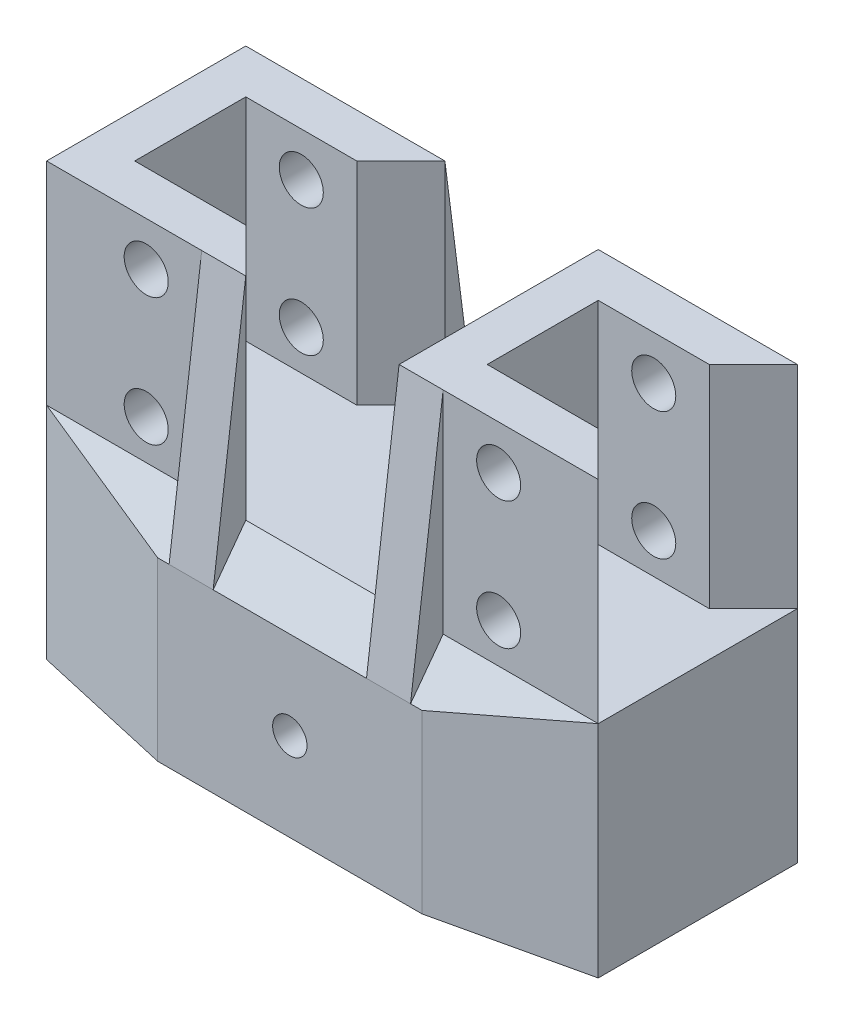
SolidWorks part; units mm, degrees
ref_plane "Front Plane" through (0, 0, 0) normal (0, 0, 1) x (1, 0, 0)
ref_plane "Top Plane" through (0, 0, 0) normal (0, 1, 0) x (1, 0, 0)
ref_plane "Right Plane" through (0, 0, 0) normal (1, 0, 0) x (0, 0, -1)
sketch "Sketch1" plane through (0, 0, 0) normal (0, 1, 0) x (1, 0, 0)
  line L0 (-20, 0) -> (20, 0)
  line L1 (-31.3, 11.3) -> (-8.7, 11.3)
  line L2 (-26.3, -6.3) -> (-13.7, -6.3)
  line L3 (-26.3, -6.3) -> (-26.3, 6.3)
  line L4 (-26.3, 6.3) -> (-13.7, 6.3)
  line L5 (-13.7, -6.3) -> (-13.7, 6.3)
  line L6 (-26.3, -6.3) -> (-13.7, 6.3) construction
  line L7 (-26.3, 6.3) -> (-13.7, -6.3) construction
  line L8 (13.7, -6.3) -> (26.3, -6.3)
  line L9 (13.7, -6.3) -> (13.7, 6.3)
  line L10 (13.7, 6.3) -> (26.3, 6.3)
  line L11 (26.3, -6.3) -> (26.3, 6.3)
  line L12 (13.7, -6.3) -> (26.3, 6.3) construction
  line L13 (13.7, 6.3) -> (26.3, -6.3) construction
  line L14 (-8.7, -11.3) -> (-8.7, 11.3)
  line L15 (-31.3, -11.3) -> (-8.7, -11.3)
  line L16 (-31.3, -11.3) -> (-31.3, 11.3)
  line L17 (8.7, 11.3) -> (31.3, 11.3)
  line L18 (31.3, -11.3) -> (31.3, 11.3)
  line L19 (8.7, -11.3) -> (31.3, -11.3)
  line L20 (8.7, -11.3) -> (8.7, 11.3)
  line L21 (-13.7, 6.3) -> (-8.7, 11.3)
  line L22 (-13.7, -6.3) -> (-8.7, -11.3)
  line L23 (26.3, -6.3) -> (31.3, -11.3)
  line L24 (26.3, 6.3) -> (31.3, 11.3)
  point P4 (0, 0)
  dimension "D1" = 40
  dimension "D2" = 12.6
  dimension "D3" = 12.6
  dimension "D4" = 12.6
  dimension "D5" = 12.6
  dimension "D6" = 5
extrude "Boss-Extrude1" add sketch "Sketch1" along normal blind 24 contours L22 L2 L3 L4 L21 L1 L16 L15 | L10 L24 L17 L20 L0 L9 | L23 L8 L9 L0 L20 L19 region at (16.9878, 0, -7.5306) region at (16.9878, 0, 7.5306) region at (-11.426, 0, 9.026)
sketch "Sketch2" plane through (0, 0, 11.3) normal (0, 0, 1) x (1, 0, 0)
  line L0 (-20, 23.5) -> (-20, 19)
  line L1 (-20, 19) -> (-20, 4.5)
  line L2 (-20, 4.5) -> (-20, 0)
  line L3 (-31.3, 0) -> (-8.7, 0) construction
  line L4 (0, -12.43) -> (0, 12.43) construction
  line L5 (20, 4.5) -> (20, 0)
  line L6 (20, 19) -> (20, 4.5)
  circle A0 centre (-20, 19) radius 2.5
  circle A1 centre (-20, 4.5) radius 2.5
  circle A2 centre (20, 4.5) radius 2.5
  circle A3 centre (20, 19) radius 2.5
  point P9 (-20, 0)
  dimension "D1" = 5
  dimension "D2" = 5
  dimension "D3" = 14.5
  dimension "D4" = 4.5
  dimension "D5" = 0
  dimension "D6" = 4.5
extrude "Cut-Extrude1" cut sketch "Sketch2" against normal through all contours L1 A0 L0 | L0 A0 L1 | L2 A1 L1 | L1 A1 L2 | A2 L5 L6 | A2 L6 L5 | A3 region at (-18.939, 19, 11.3) region at (-18.939, 4.5, 11.3) region at (-21.061, 4.5, 11.3) region at (-21.061, 19, 11.3) region at (21.061, 4.5, 11.3) region at (18.939, 4.5, 11.3) region at (18.2822, 20.7178, 11.3)
sketch "Sketch3" plane through (0, 0, 0) normal (0, -1, 0) x (1, 0, 0)
  line L1 (-31.3, -11.3) -> (31.3, -11.3)
  line L2 (-31.3, -11.3) -> (-31.3, 11.3)
  line L3 (-31.3, 11.3) -> (31.3, 11.3)
  line L4 (31.3, -11.3) -> (31.3, 11.3)
  line L5 (-31.3, -11.3) -> (31.3, 11.3) construction
  line L6 (-31.3, 11.3) -> (31.3, -11.3) construction
  point P0 (0, 0)
extrude "Boss-Extrude2" add sketch "Sketch3" along normal blind 5
sketch "Sketch4" plane through (0, -5, 0) normal (0, -1, 0) x (1, 0, 0)
  line L0 (-15, -15) -> (-15, 15)
  line L1 (-10, -10) -> (10, -10)
  line L2 (-10, -10) -> (-10, 10)
  line L3 (-10, 10) -> (10, 10)
  line L4 (10, -10) -> (10, 10)
  line L5 (-10, -10) -> (10, 10) construction
  line L6 (-10, 10) -> (10, -10) construction
  line L7 (-15, 15) -> (15, 15)
  line L8 (15, -15) -> (15, 15)
  line L9 (-15, -15) -> (15, -15)
  point P0 (0, 0)
  dimension "D1" = 20
  dimension "D2" = 20
  dimension "D3" = 5
extrude "Boss-Extrude3" add sketch "Sketch4" along normal blind 20
sketch "Sketch6" plane through (0, -25, 0) normal (0, -1, 0) x (1, 0, 0)
  line L0 (15, 15) -> (31.3, 11.3)
  line L1 (31.3, 11.3) -> (31.3, -11.3)
  line L2 (31.3, -11.3) -> (15, -15)
  line L3 (15, -15) -> (-15, -15)
  line L4 (-15, -15) -> (-31.3, -11.3)
  line L5 (-31.3, -11.3) -> (-31.3, 11.3)
  line L6 (-31.3, 11.3) -> (-15, 15)
  line L7 (-15, 15) -> (15, 15)
  line L9 (-10, -10) -> (10, -10)
  line L10 (-10, -10) -> (-10, 10)
  line L11 (-10, 10) -> (10, 10)
  line L12 (10, -10) -> (10, 10)
  line L13 (-10, -10) -> (10, 10) construction
  line L14 (-10, 10) -> (10, -10) construction
  point P4 (0, 0)
extrude "Boss-Extrude4" add sketch "Sketch6" against normal blind 20
sketch "Sketch8" plane through (0, -5, 0) normal (0, -1, 0) x (1, 0, 0)
  line L0 (4, -2.5) -> (4, 2.5)
  line L1 (8, -2.3555) -> (8, 2.3555)
  line L2 (8, -5) -> (8, 5)
  line L3 (4, 2.5) -> (8, 5)
  line L4 (4, -2.5) -> (8, -5)
  line L5 (8, -2.3555) -> (10, -2.3555)
  line L6 (8, 2.3555) -> (10, 2.3555)
  line L7 (10, 2.3555) -> (10, -2.3555)
  line L8 (10, -10) -> (10, 10) construction
  line L9 (-10, -10) -> (10, -10) construction
  line L10 (-2.3555, -8) -> (2.3555, -8)
  line L11 (2.3555, -8) -> (2.3555, -10)
  line L12 (2.3555, -10) -> (-2.3555, -10)
  line L13 (-2.3555, -8) -> (-2.3555, -10)
  line L14 (-2.5, -4) -> (2.5, -4)
  line L15 (2.5, -4) -> (5, -8)
  line L16 (-5, -8) -> (5, -8)
  line L17 (-2.5, -4) -> (-5, -8)
  line L18 (-8, 2.3555) -> (-8, -2.3555)
  line L19 (-8, -2.3555) -> (-10, -2.3555)
  line L20 (-10, -2.3555) -> (-10, 2.3555)
  line L21 (-8, 2.3555) -> (-10, 2.3555)
  line L22 (-4, 2.5) -> (-4, -2.5)
  line L23 (-4, -2.5) -> (-8, -5)
  line L24 (-8, 5) -> (-8, -5)
  line L25 (-4, 2.5) -> (-8, 5)
  line L26 (2.3555, 8) -> (-2.3555, 8)
  line L27 (-2.3555, 8) -> (-2.3555, 10)
  line L28 (-2.3555, 10) -> (2.3555, 10)
  line L29 (2.3555, 8) -> (2.3555, 10)
  line L30 (2.5, 4) -> (-2.5, 4)
  line L31 (-2.5, 4) -> (-5, 8)
  line L32 (5, 8) -> (-5, 8)
  line L33 (2.5, 4) -> (5, 8)
  point P2 (4, 0)
  point P5 (8, 0)
  point P8 (8, 0)
  point P17 (10, 0)
  point P43 (0, 0)
  line M13 (-10, -10) -> (10, -10)
  line M14 (10, -10) -> (10, 10)
  line M15 (10, 10) -> (-10, 10)
  line M16 (-10, 10) -> (-10, -10)
  dimension "D1" = 2
  dimension "D2" = 10
  dimension "D3" = 4.711
  dimension "D4" = 5
  dimension "D5" = 4
  dimension "D6" = 0
  dimension "D7" = 10
  dimension "D8" = 0
  dimension "D9" = 4
extrude "Boss-Extrude5" add sketch "Sketch8" along normal blind 20 contours L0 L4 L2 L1 L3 | L6 L1 L5 M14 | L26 L29 L27 M15 | L30 L33 L32 L26 L31 | L18 L21 L19 M16 | L22 L25 L24 L18 L23 | L10 L13 L11 M13 | L14 L17 L16 L10 L15 region at (6.2222, -5, 0) region at (9, -5, 0) region at (0, -5, -9) region at (0, -5, 9) region at (0, -5, -6.2222) region at (0, -5, 6.2222) region at (-9, -5, 0) region at (-6.2222, -5, 0)
sketch "Sketch9" plane through (0, -5, 0) normal (0, 1, 0) x (1, 0, 0)
  line L0 (-15, 15) -> (15, 15) construction
  line L1 (8.7, 11.3) -> (13.7, 11.3)
  line L2 (8.7, 11.3) -> (8.7, 15)
  line L3 (8.7, 15) -> (13.7, 15)
  line L4 (13.7, 11.3) -> (13.7, 15)
  line L5 (13.7, -6.3) -> (13.7, 6.3) construction
  line L6 (-26.95, 0) -> (26.95, 0) construction
  line L7 (8.7, -15) -> (13.7, -15)
  line L8 (13.7, -11.3) -> (13.7, -15)
  line L9 (8.7, -11.3) -> (13.7, -11.3)
  line L10 (8.7, -11.3) -> (8.7, -15)
  line L11 (0, -16.5) -> (0, 16.5) construction
  line L12 (-8.7, 15) -> (-13.7, 15)
  line L13 (-13.7, 11.3) -> (-13.7, 15)
  line L14 (-8.7, 11.3) -> (-13.7, 11.3)
  line L15 (-8.7, 11.3) -> (-8.7, 15)
  line L16 (-8.7, -11.3) -> (-8.7, -15)
  line L17 (-8.7, -11.3) -> (-13.7, -11.3)
  line L18 (-13.7, -11.3) -> (-13.7, -15)
  line L19 (-8.7, -15) -> (-13.7, -15)
  dimension "D1" = 0
extrude "Boss-Extrude6" add sketch "Sketch9" along normal blind 29
chamfer "Chamfer1" distance 29 distance2 3.7 4 edges at (11.2, 24, -15) (-11.2, 24, -15) (-11.2, 24, 15) (11.2, 24, 15) first distance on face at (0, 1.3333, -15) first distance on face at (0, 1.3333, 15)
chamfer "Chamfer3" distance 5 distance2 3.7 1 edges at (0, -5, -11.3) first distance on face at (0, -2.5, -11.3)
chamfer "Chamfer4" distance 5 distance2 3.7 4 edges at (22.5, -5, 11.3) (-22.5, -5, 11.3) (22.5, -5, -11.3) (-22.5, -5, -11.3) first distance on face at (22.5, 19, 11.3) first distance on face at (-17.5, 19, 11.3) first distance on face at (22.5, 19, -11.3) first distance on face at (-17.5, 19, -11.3)
chamfer "Chamfer5" distance 5 distance2 3.7 1 edges at (0, -5, 11.3) first distance on face at (0, -2.5, 11.3)
sketch "Sketch11" plane through (0, 0, -4) normal (0, 0, 1) x (1, 0, 0)
  line L0 (0, -5) -> (0, -25)
  line L1 (8.7, -5) -> (-8.7, -5) construction
  line L2 (15, -25) -> (-15, -25) construction
  circle A0 centre (0, -15) radius 1.95
  dimension "D1" = 3.9
extrude "Cut-Extrude2" cut sketch "Sketch11" against normal through all and the other way through all contours A0
